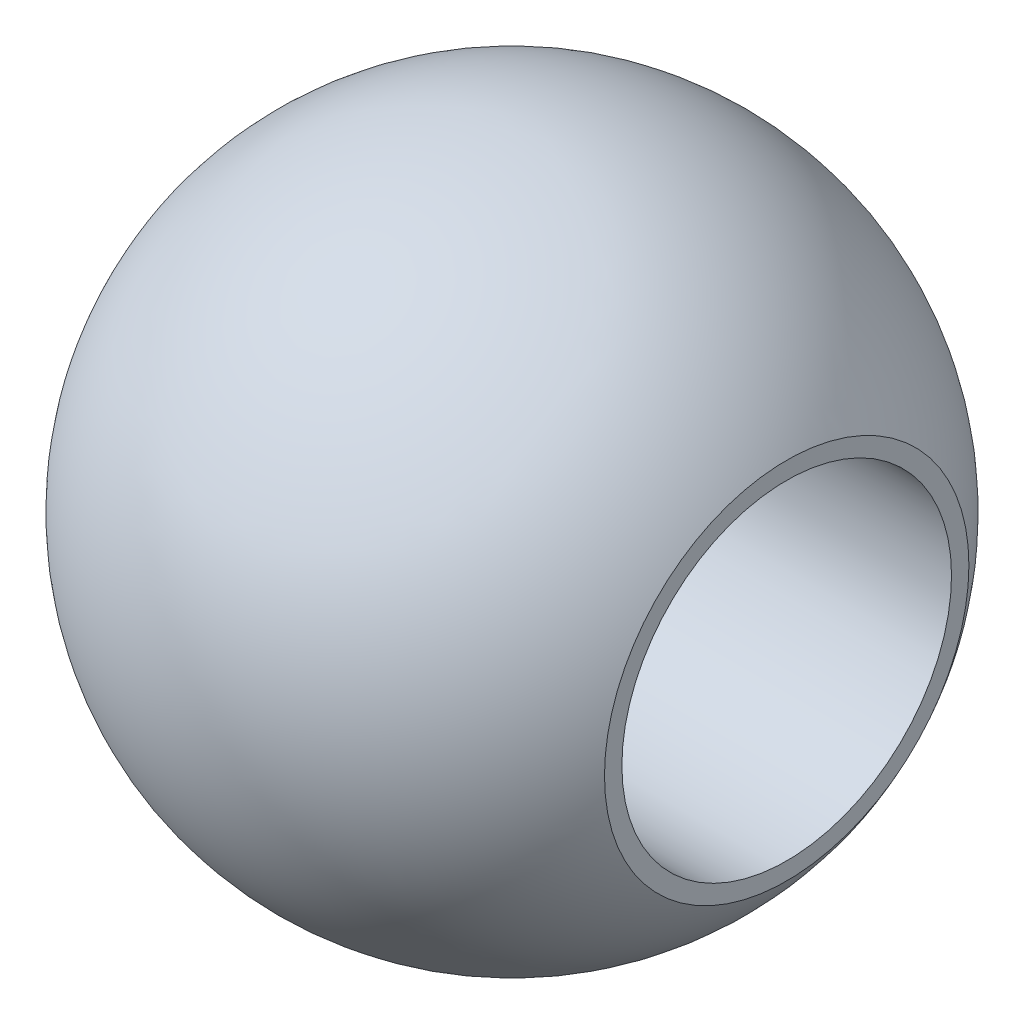
SolidWorks part; units mm, degrees
ref_plane "前视基准面" through (0, 0, 0) normal (0, 0, 1) x (1, 0, 0)
ref_plane "上视基准面" through (0, 0, 0) normal (0, 1, 0) x (1, 0, 0)
ref_plane "右视基准面" through (0, 0, 0) normal (1, 0, 0) x (0, 0, -1)
sketch "草图1" plane through (0, 0, 0) normal (0, 1, 0) x (1, 0, 0)
  line L0 (0, 3) -> (0, -3)
  circle A0 centre (0, 0) radius 3
  dimension "D1" = 6
revolve "旋转1" add sketch "草图1" angle 360 about L0 region at (1.2732, 0, 0)
sketch "草图2" plane through (0, 0, 0) normal (0, 1, 0) x (1, 0, 0)
  line L1 (2.5, -3.0567) -> (-2.5, -3.0567)
  line L2 (2.5, -3.0567) -> (2.5, 3.0567)
  line L3 (2.5, 3.0567) -> (-2.5, 3.0567)
  line L4 (-2.5, -3.0567) -> (-2.5, 3.0567)
  line L5 (2.5, -3.0567) -> (-2.5, 3.0567) construction
  line L6 (2.5, 3.0567) -> (-2.5, -3.0567) construction
  line L7 (-3.7949, 3.8183) -> (4.3359, 3.8183)
  line L8 (-3.7949, 3.8183) -> (-3.7949, -5.018)
  line L9 (-3.7949, -5.018) -> (4.3359, -5.018)
  line L10 (4.3359, 3.8183) -> (4.3359, -5.018)
  point P0 (0, 0)
  dimension "D1" = 5
extrude "切除-拉伸1" cut sketch "草图2" against normal blind 10 and the other way blind 10
sketch "草图3" plane through (2.5, 0, 0) normal (1, 0, 0) x (0, 0, -1)
  circle A0 centre (0, 0) radius 1.5
  dimension "D1" = 3
extrude "切除-拉伸2" cut sketch "草图3" against normal blind 10
sketch "草图4" plane through (0, 0, 0) normal (1, 0, 0) x (0, 0, -1)
  point P0 (0, 0)
